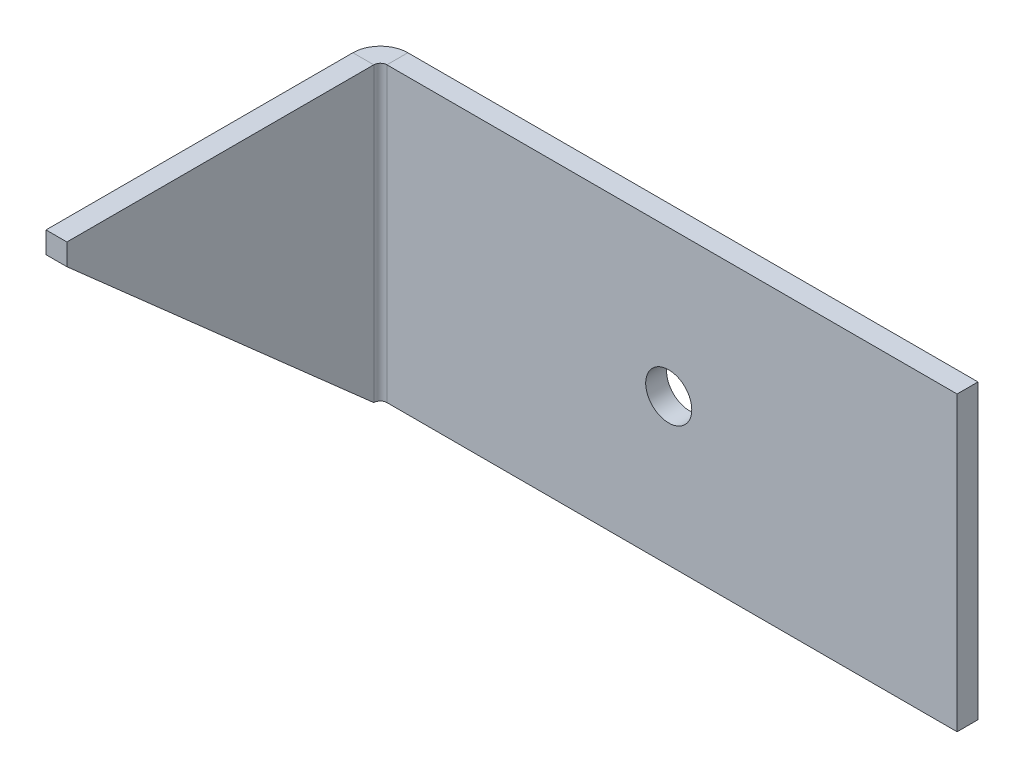
SolidWorks part; units mm, degrees
note: The reader was unsure of these and kept them because the rebuilt part matched: flange length of "Edge-Flange1".
material "6061-T6 (SS)"
ref_plane "X-Y Datum" through (0, 0, 0) normal (0, 0, 1) x (1, 0, 0)
ref_plane "X-Z Datum" through (0, 0, 0) normal (0, 1, 0) x (1, 0, 0)
ref_plane "Y-Z Datum" through (0, 0, 0) normal (1, 0, 0) x (0, 0, -1)
sketch "Sketch1" plane through (0, 0, 0) normal (0, 0, 1) x (1, 0, 0)
  line L1 (-45.4025, -22.225) -> (45.4025, -22.225)
  line L2 (-45.4025, -22.225) -> (-45.4025, 22.225)
  line L3 (-45.4025, 22.225) -> (45.4025, 22.225)
  line L4 (45.4025, -22.225) -> (45.4025, 22.225)
  line L5 (-45.4025, -22.225) -> (45.4025, 22.225) construction
  line L6 (-45.4025, 22.225) -> (45.4025, -22.225) construction
  circle A0 centre (0, 0) radius 3 construction
  point P0 (0, 0)
  dimension "D3" = 6
  dimension "D1" = 90.805
  dimension "D2" = 44.45
base flange "Base-Flange1" sketch "Sketch1" thickness 3.175 reverse thickness direction yes parameters "D1"=10
edge flange "Edge-Flange1" sketch "Sketch8" flange angle 90 flange length 50.8 flange position material inside bend radius 1 thickness 3.175 relief rectangular parameters "D6"=10
sketch "Sketch8" plane through (-45.4025, 0, 3.175) normal (1, 0, 0) x (0, 1, 0)
  line L2 (-22.225, 0) -> (-22.225, 47.625)
  line L3 (-22.225, 47.625) -> (22.225, 47.625)
  line L4 (22.225, 47.625) -> (22.225, 0)
  line L5 (22.225, 0) -> (-22.225, 0) construction
  line L6 (22.225, 0) -> (-22.225, 0)
bend "EdgeBend1" bend radius 1 bend angle 90 parameters "D5"=1
sketch "Sketch9" plane through (-45.4025, 0, 0) normal (-1, 0, 0) x (0, 0, 1)
  line L0 (50.8, 18.9624) -> (4.175, -22.225)
  line L1 (50.8, 22.225) -> (50.8, 18.9624)
  line L2 (50.8, 22.225) -> (50.8, -22.225) construction
extrude "Cut-Extrude1" cut sketch "Sketch9" against normal blind 3.175 and the other way through all
edge flange "Edge-Flange2" [suppressed] sketch "Sketch12" flange angle 90 flange position material outside bend radius 1 thickness 3.175
sketch "Sketch12" [suppressed] plane through (45.4025, 0, 3.175) normal (-1, 0, 0) x (0, -1, 0)
  line L2 (-22.225, 0) -> (-22.225, 47.625)
  line L3 (-22.225, 47.625) -> (22.225, 47.625)
  line L4 (22.225, 47.625) -> (22.225, 0)
  line L5 (22.225, 0) -> (-22.225, 0) construction
  line L6 (22.225, 0) -> (-22.225, 0)
bend "EdgeBend2" [suppressed] bend radius 1 bend angle 90 parameters "D5"=1, "D6"=10, "D7"=50.8
sketch "Sketch13" [suppressed] plane through (48.5775, 0, 0) normal (1, 0, 0) x (0, 0, -1)
  line L0 (-50.8, 18.9624) -> (-4.175, -22.225)
  line L1 (-50.8, 22.225) -> (-50.8, 18.9624)
  line L2 (-50.8, -22.225) -> (-50.8, 22.225) construction
extrude "Cut-Extrude2" [suppressed] cut sketch "Sketch13" against normal blind 3.175 and the other way through all
hole_wizard "M6 Clearance Hole2" [suppressed] positions "Sketch25" profile "Sketch20" hole size "M6" standard "ANSI Metric"
sketch "Sketch25" [suppressed] plane through (0, 0, 3.175) normal (0, 0, 1) x (1, 0, 0)
  point P0 (0, 0)
sketch "Sketch20" plane through (0, 0, 3.175) normal (1, 0, 0) x (0, -1, 0)
  line L0 (0, 0) -> (0, 3.175)
  line L1 (0, 3.175) -> (3.5, 3.175)
  line L2 (3.5, 3.175) -> (3.5, 0)
  line L5 (3.5, 0) -> (0, 0)
  line L11 (0, -6.35) -> (0, 107.95) construction
  dimension "Thru Hole Dia." = 7
  dimension "Thru Hole Depth" = 3.175
sketch "Sketch28" plane through (0, 0, 3.175) normal (0, 0, 1) x (1, 0, 0)
  circle A0 centre (1.5875, 0) radius 3.5 construction
  circle A1 centre (1.5875, 0) radius 3.5
  point P0 (1.5875, 0)
hole_wizard "M6 Clearance Hole3" positions "Sketch28" profile "Sketch29" hole size "M6" standard "ANSI Metric" end condition through all
sketch "Sketch29" plane through (1.5875, 0, 3.175) normal (1, 0, 0) x (0, -1, 0)
  line L0 (0, 0) -> (0, 3.175)
  line L1 (0, 3.175) -> (3.5, 3.175)
  line L2 (3.5, 3.175) -> (3.5, 0)
  line L5 (3.5, 0) -> (0, 0)
  line L11 (0, -6.35) -> (0, 107.95) construction
  dimension "Thru Hole Dia." = 7
  dimension "Thru Hole Depth" = 3.175
sketch "Sketch30" [suppressed] plane through (0, 0, 3.175) normal (0, 0, 1) x (1, 0, 0)
  circle A0 centre (1.5875, 0) radius 3.5 construction
  circle A1 centre (1.5875, 0) radius 3.5
  point P0 (1.5875, 0)
hole_wizard "M6 Clearance Hole4" [suppressed] positions "Sketch30" profile "Sketch31" hole size "M6" standard "ANSI Metric"
sketch "Sketch31" plane through (1.5875, 0, 3.175) normal (1, 0, 0) x (0, -1, 0)
  line L0 (0, 0) -> (0, 3.175)
  line L1 (0, 3.175) -> (3.5, 3.175)
  line L2 (3.5, 3.175) -> (3.5, 0)
  line L5 (3.5, 0) -> (0, 0)
  line L11 (0, -6.35) -> (0, 107.95) construction
  dimension "Thru Hole Dia." = 7
  dimension "Thru Hole Depth" = 3.175
sketch "Bend-Lines1" [suppressed] plane through (0, 0, 0) normal (0, 1, 0) x (1, 0, 0)
sketch "Bounding-Box1" [suppressed] plane through (0, 0, 0) normal (0, 1, 0) x (1, 0, 0)
sheet metal parameters "Sheet-Metal1" thickness 3.175 parameters "D1"=10
flat pattern "Flat-Pattern1" [suppressed]
sketch "Bend-Lines2" plane through (0, 0, 0) normal (0, 1, 0) x (1, 0, 0)
sketch3d "Bounding-Box2" [suppressed]
  line L0 (43.815, -22.225, 0) -> (-43.815, -22.225, 0) construction
  line L1 (43.815, 22.225, 0) -> (-43.815, 22.225, 0) construction
  line L2 (43.815, -22.225, 0) -> (43.815, 22.225, 0) construction
  line L3 (-43.815, -22.225, 0) -> (-43.815, 22.225, 0) construction
sketch "Sketch25-1" [suppressed] plane through (0, 0, 3.175) normal (0, 0, 1) x (1, 0, 0)
  point P0 (0, 0)
sketch "Sketch24-1" plane through (0, 0, 3.175) normal (0, 0, 1) x (1, 0, 0)
  point P0 (0, 0)
sheet metal parameters "Sheet-Metal2" thickness 3.175 parameters "D1"=10
flat pattern "Flat-Pattern1"
sketch "Bend-Lines2" plane through (0, 0, 0) normal (0, 0, -1) x (-1, 0, 0)
  line L0 (43.2597, -22.225) -> (43.2597, 22.225) construction
  line L1 (43.2597, -22.225) -> (43.2597, 22.225) construction
sketch3d "Bounding-Box2" [suppressed]
  line L0 (91.9169, -22.225, 0) -> (-45.4025, -22.225, 0) construction
  line L1 (91.9169, 22.225, 0) -> (-45.4025, 22.225, 0) construction
  line L2 (91.9169, -22.225, 0) -> (91.9169, 22.225, 0) construction
  line L3 (-45.4025, -22.225, 0) -> (-45.4025, 22.225, 0) construction
bend of the flat pattern "Flatten-<EdgeBend1>1"
sheet metal parameters "Sheet-Metal3" thickness 3.175 parameters "D1"=10
flat pattern "Flat-Pattern1"
sketch "Bend-Lines2" plane through (0, 0, 0) normal (0, 0, -1) x (-1, 0, 0)
  line L0 (43.2597, -22.225) -> (43.2597, 22.225) construction
  line L1 (43.2597, -22.225) -> (43.2597, 22.225) construction
sketch3d "Bounding-Box2" [suppressed]
  line L0 (91.9169, -22.225, 0) -> (-45.4025, -22.225, 0) construction
  line L1 (91.9169, 22.225, 0) -> (-45.4025, 22.225, 0) construction
  line L2 (91.9169, -22.225, 0) -> (91.9169, 22.225, 0) construction
  line L3 (-45.4025, -22.225, 0) -> (-45.4025, 22.225, 0) construction
bend of the flat pattern "Flatten-<EdgeBend1>1"
sheet metal parameters "Sheet-Metal4" thickness 3.175 parameters "D1"=10
flat pattern "Flat-Pattern1"
sketch "Bend-Lines2" plane through (0, 0, 0) normal (0, 0, -1) x (-1, 0, 0)
  line L0 (-44.8523, 22.1374) -> (-44.8523, -22.1374) construction
  line L1 (-44.8523, 22.1374) -> (-44.8523, -22.1374) construction
sketch3d "Bounding-Box2" [suppressed]
  line L0 (43.8201, -22.1374, 0) -> (-93.5095, -22.1374, 0) construction
  line L1 (43.8201, 22.1374, 0) -> (-93.5095, 22.1374, 0) construction
  line L2 (43.8201, -22.1374, 0) -> (43.8201, 22.1374, 0) construction
  line L3 (-93.5095, -22.1374, 0) -> (-93.5095, 22.1374, 0) construction
bend of the flat pattern "Flatten-<EdgeBend2>1"
sheet metal parameters "Sheet-Metal5" thickness 3.175 parameters "D1"=10
flat pattern "Flat-Pattern1"
sketch "Bend-Lines2" plane through (0, 0, 0) normal (0, 0, -1) x (-1, 0, 0)
  line L0 (-46.4347, 22.225) -> (-46.4347, -22.225) construction
  line L1 (-46.4347, 22.225) -> (-46.4347, -22.225) construction
sketch3d "Bounding-Box2" [suppressed]
  line L0 (45.4025, -22.225, 0) -> (-95.0919, -22.225, 0) construction
  line L1 (45.4025, 22.225, 0) -> (-95.0919, 22.225, 0) construction
  line L2 (45.4025, -22.225, 0) -> (45.4025, 22.225, 0) construction
  line L3 (-95.0919, -22.225, 0) -> (-95.0919, 22.225, 0) construction
bend of the flat pattern "Flatten-<EdgeBend2>1"
sheet metal parameters "Sheet-Metal8" thickness 3.175 parameters "D1"=10
flat pattern "Flat-Pattern1"
sketch "Bend-Lines2" plane through (0, 0, 0) normal (0, 0, -1) x (-1, 0, 0)
  line L0 (-46.4347, 22.225) -> (-46.4347, -22.225) construction
  line L1 (-46.4347, 22.225) -> (-46.4347, -22.225) construction
sketch3d "Bounding-Box2" [suppressed]
  line L0 (45.4025, -22.225, 0) -> (-95.0919, -22.225, 0) construction
  line L1 (45.4025, 22.225, 0) -> (-95.0919, 22.225, 0) construction
  line L2 (45.4025, -22.225, 0) -> (45.4025, 22.225, 0) construction
  line L3 (-95.0919, -22.225, 0) -> (-95.0919, 22.225, 0) construction
bend of the flat pattern "Flatten-<EdgeBend2>1"
sheet metal parameters "Sheet-Metal10" thickness 3.175 parameters "D1"=10
flat pattern "Flat-Pattern1"
sketch "Bend-Lines2" plane through (0, 0, 0) normal (0, 0, -1) x (-1, 0, 0)
  line L0 (43.2597, -22.225) -> (43.2597, 22.225) construction
  line L1 (43.2597, -22.225) -> (43.2597, 22.225) construction
sketch3d "Bounding-Box2" [suppressed]
  line L0 (91.9169, -22.225, 0) -> (-45.4025, -22.225, 0) construction
  line L1 (91.9169, 22.225, 0) -> (-45.4025, 22.225, 0) construction
  line L2 (91.9169, -22.225, 0) -> (91.9169, 22.225, 0) construction
  line L3 (-45.4025, -22.225, 0) -> (-45.4025, 22.225, 0) construction
bend of the flat pattern "Flatten-<EdgeBend1>1"
sheet metal parameters "Sheet-Metal11" thickness 3.175 parameters "D1"=10
flat pattern "Flat-Pattern1"
sketch "Bend-Lines2" plane through (0, 0, 0) normal (0, 0, -1) x (-1, 0, 0)
  line L0 (-46.4347, 22.225) -> (-46.4347, -22.225) construction
  line L1 (-46.4347, 22.225) -> (-46.4347, -22.225) construction
sketch3d "Bounding-Box2" [suppressed]
  line L0 (45.4025, -22.225, 0) -> (-95.0919, -22.225, 0) construction
  line L1 (45.4025, 22.225, 0) -> (-95.0919, 22.225, 0) construction
  line L2 (45.4025, -22.225, 0) -> (45.4025, 22.225, 0) construction
  line L3 (-95.0919, -22.225, 0) -> (-95.0919, 22.225, 0) construction
bend of the flat pattern "Flatten-<EdgeBend2>1"
